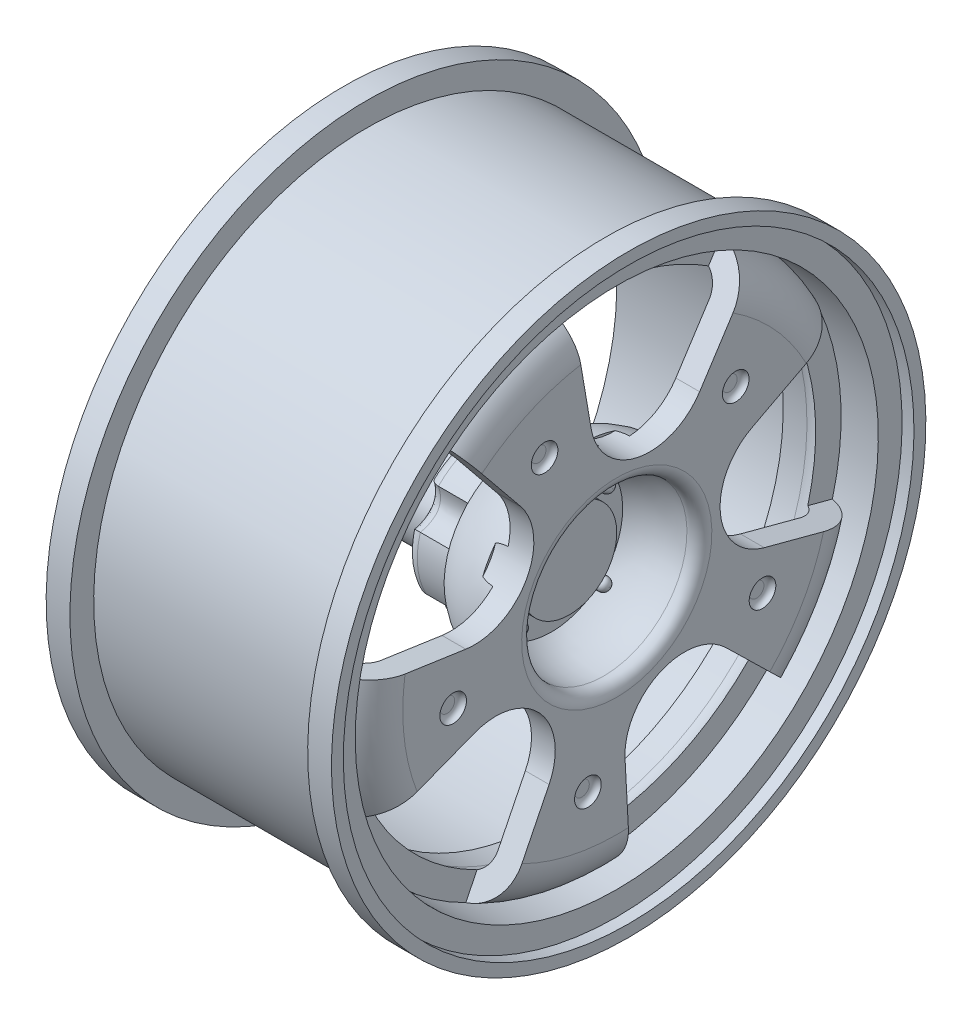
SolidWorks part; units mm, degrees
ref_plane "Front Plane" through (0, 0, 0) normal (0, 0, 1) x (1, 0, 0)
ref_plane "Top Plane" through (0, 0, 0) normal (0, 1, 0) x (1, 0, 0)
ref_plane "Right Plane" through (0, 0, 0) normal (1, 0, 0) x (0, 0, -1)
sketch "Sketch1" plane through (0, 0, 0) normal (0, 0, 1) x (1, 0, 0)
  line L1 (11, -1) -> (7, -1)
  line L2 (0, 0) -> (0, -23) construction
  line L3 (-11, -1) -> (-11, 1)
  line L4 (-11, 1) -> (-12, 1)
  line L5 (-12, 1) -> (-12, 2)
  line L6 (-12, 2) -> (-10, 2)
  line L7 (12, 2) -> (12, 1)
  line L8 (12, 1) -> (11, 1)
  line L9 (11, 1) -> (11, -1)
  line L10 (-10, 2) -> (-10, 0)
  line L11 (-10, 0) -> (10, 0)
  line L12 (10, 0) -> (10, 2)
  line L13 (10, 2) -> (12, 2)
  line L14 (11, -5) -> (11, -15)
  line L15 (7, -3) -> (5, -3)
  line L16 (5, -3) -> (5, -1)
  line L17 (-11, -1) -> (5, -1)
  line L18 (9, -5) -> (9, -13.9591)
  line L19 (5.5, -17) -> (5.5, -19)
  line L20 (5.5, -19) -> (7, -19)
  line L21 (7, -19) -> (7, -23)
  line L22 (7, -23) -> (3.5, -23)
  line L23 (3.5, -15.9725) -> (3.5, -23)
  line L24 (-26.5983, -23) -> (26.5983, -23) construction
  arc A0 (7, -1) -> (11, -5) centre (7, -5) cw
  arc A1 (7, -3) -> (9, -5) centre (7, -5) cw
  arc A2 (9.8969, -15.9947) -> (5.5, -17) centre (9.1755, -22.9574) ccw
  arc A3 (9, -13.9591) -> (3.5, -15.9725) centre (9.1755, -22.9574) ccw
  arc A4 (11, -15) -> (9.8969, -15.9947) centre (10, -15) cw
  dimension "D3" = 2
  dimension "D7" = 1
  dimension "D21" = 2
  dimension "D8" = 7
  dimension "D19" = 10
  dimension "D23" = 2
  dimension "D2" = 2
  dimension "D4" = 4
  dimension "D5" = 2
  dimension "D6" = 2
  dimension "D9" = 1
  dimension "D10" = 2
  dimension "D11" = 1.5
  dimension "D12" = 4
  dimension "D13" = 2
  dimension "D14" = 1
  dimension "D15" = 20
  dimension "D16" = 2
  dimension "D17" = 9
  dimension "D18" = 4
  dimension "D20" = 3.5
  dimension "D22" = 25
revolve "Revolve2" add sketch "Sketch1" angle 360 about L24
sketch "Sketch2" plane through (11, 0, 0) normal (1, 0, 0) x (0, 0, -1)
  line L0 (19.4835, -12.7826) -> (11.3663, -17.0393)
  line L1 (12.4031, -26.2994) -> (21.2606, -28.6556)
  arc A0 (12.4031, -26.2994) -> (11.3663, -17.0393) centre (13.6885, -21.4674) cw
  circle A2 centre (0, -23) radius 22 construction
  arc A3 (19.4835, -12.7826) -> (21.2606, -28.6556) centre (0, -23) cw
  dimension "D1" = 5
extrude "Cut-Extrude3" cut sketch "Sketch2" against normal blind 3
pattern_circular "CirPattern1" count 5 over 360 about axis through (11, -23, 0) along (-1, 0, 0) of "Cut-Extrude3"
sketch "Sketch3" plane through (5.5, 0, 0) normal (1, 0, 0) x (0, 0, -1)
  circle A0 centre (3.6615, -19.6378) radius 0.5257
extrude "Boss-Extrude1" add sketch "Sketch3" along normal blind 1.5
fillet "Fillet1" radius 0.5 1 edges at (7, -19.1121, -3.6615) type face fillet first side face at (7, -19.1121, -3.6615) second side face at (7, -19.1121, -3.6615)
pattern_circular "CirPattern3" count 4 over 360 about axis through (5.5, -23, 0) along (-1, 0, 0) of "Boss-Extrude1", "Fillet1"
sketch "Sketch4" plane through (11, 0, 0) normal (1, 0, 0) x (0, 0, -1)
  circle A0 centre (10.0065, -13.3621) radius 1.1197
extrude "Cut-Extrude4" cut sketch "Sketch4" against normal blind 0.5
fillet "Fillet3" radius 0.5 1 edges at (10.5, -12.2424, -10.0065)
pattern_circular "CirPattern4" count 5 over 360 about axis through (11, -23, 0) along (-1, 0, 0) of "Cut-Extrude4", "Fillet3"
sketch "Sketch6" plane through (3.5, 0, 0) normal (-1, 0, 0) x (0, 0, 1)
  circle A0 centre (0, -23) radius 6.2805
extrude "Boss-Extrude2" add sketch "Sketch6" along normal blind 4
sketch "Sketch8" plane through (-0.5, 0, 0) normal (-1, 0, 0) x (0, 0, 1)
  circle A0 centre (0, -23) radius 6.2805 construction
  circle A1 centre (0, -23) radius 6.2805 construction
  arc A2 (-2.7754, -17.366) -> (0.1664, -16.7217) centre (0, -23) cw
  spline S0 degree 2 poles (0.1664, -16.7217) (-1.0004, -18.7007) (-2.7754, -17.366) knots 0 0 0 1 1 1
extrude "Cut-Extrude6" cut sketch "Sketch8" against normal blind 4
pattern_circular "CirPattern5" count 5 over 360 about axis through (-0.5, -23, 0) along (-1, 0, 0) of "Cut-Extrude6"
fillet "Fillet4" radius 1 10 edges at (-0.5, -26.1738, -5.4196) (-0.5, -18.8264, -4.6932) (-0.5, -17.2468, 2.519) (-0.5, -23.6179, 6.25) (-0.5, -29.1351, 1.3437)
sketch "Sketch9" plane through (-0.5, 0, 0) normal (-1, 0, 0) x (0, 0, 1)
  circle A0 centre (0, -23) radius 3.972
extrude "Boss-Extrude3" add sketch "Sketch9" along normal blind 15
sketch "Sketch10" plane through (-15.5, 0, 0) normal (-1, 0, 0) x (0, 0, 1)
  line L1 (2.1984, -21) -> (-2.1984, -21)
  line L3 (2.1984, -25) -> (-2.1984, -25)
  arc A0 (-2.1984, -21) -> (-2.1984, -25) centre (0, -23) ccw
  circle A1 centre (0, -23) radius 3.972 construction
  arc A2 (2.1984, -25) -> (2.1984, -21) centre (0, -23) ccw
  point P0 (0, -23)
  point P9 (2.972, -23)
  dimension "D2" = 1
  dimension "D1" = 4
extrude "Cut-Extrude7" cut sketch "Sketch10" against normal blind 15
sketch "Sketch11" plane through (-15.5, 0, 0) normal (-1, 0, 0) x (0, 0, 1)
  circle A0 centre (0, -23) radius 2.972
  arc A1 (2.1984, -25) -> (2.1984, -21) centre (0, -23) ccw construction
extrude "Cut-Extrude8" cut sketch "Sketch11" against normal blind 0.5
fillet "Fillet6" radius 0.5 2 edges at (-15, -25, 0) (-15, -21, 0)
